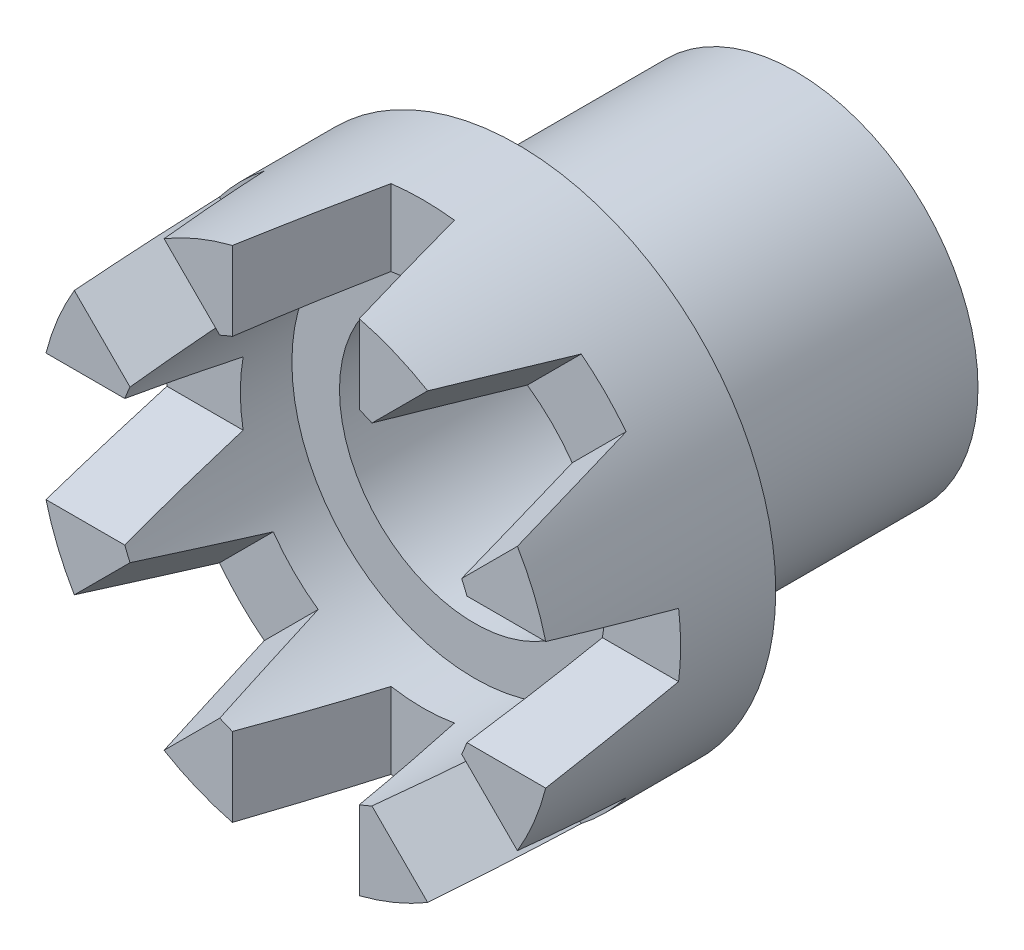
SolidWorks part; units mm, degrees
ref_plane "Спереди" through (0, 0, 0) normal (0, 0, 1) x (1, 0, 0)
ref_plane "Сверху" through (0, 0, 0) normal (0, 1, 0) x (1, 0, 0)
ref_plane "Справа" through (0, 0, 0) normal (1, 0, 0) x (0, 0, -1)
sketch "Эскиз1" plane through (0, 0, 0) normal (1, 0, 0) x (0, 0, -1)
  line L0 (0, 0) -> (130, 0) construction
  line L1 (0, 46) -> (0, 65)
  line L2 (0, 65) -> (56, 65)
  line L3 (56, 65) -> (56, 46)
  line L4 (56, 46) -> (126, 46)
  line L5 (126, 46) -> (126, 32)
  line L6 (126, 32) -> (123, 32)
  line L7 (123, 32) -> (123, 34)
  line L8 (123, 34) -> (45, 34)
  line L9 (45, 34) -> (45, 46)
  line L10 (45, 46) -> (0, 46)
  dimension "D1" = 19
  dimension "D2" = 56
  dimension "D3" = 70
  dimension "D4" = 14
  dimension "D5" = 3
  dimension "D6" = 2
  dimension "D7" = 78
  dimension "D8" = 46
  dimension "D9" = 34
revolve "Повернуть1" add sketch "Эскиз1" angle 360 about L0
sketch "Эскиз2" plane through (0, 0, 0) normal (1, 0, 0) x (0, 0, -1)
  line L0 (28, 0) -> (-22, 0) construction
  line L1 (0, 16) -> (0, -16)
  line L2 (0, 65) -> (0, -65) construction
  line L3 (0, -16) -> (32, -8)
  line L4 (32, -8) -> (32, 8)
  line L5 (0, 16) -> (32, 8)
  point P3 (32, 0)
  point P11 (0, 0)
extrude "Вытянуть1" cut sketch "Эскиз2" against normal blind 65 and the other way blind 65
sketch "Эскиз3" plane through (0, 0, 0) normal (0, 1, 0) x (1, 0, 0)
  line L0 (0, 28) -> (0, -22) construction
  line L1 (-16, 0) -> (16, 0)
  line L2 (16, 0) -> (8, 32)
  line L3 (8, 32) -> (-8, 32)
  line L4 (-16, 0) -> (-8, 32)
  point P3 (0, 32)
  point P9 (0, 0)
extrude "Вытянуть2" cut sketch "Эскиз3" against normal blind 65 and the other way blind 65
ref_plane "Плоскость4" through (0, 0, 0) normal (-0.7071, 0.7071, 0) x (-0.7071, -0.7071, 0)
sketch "Эскиз4" plane through (0, 0, 0) normal (-0.7071, 0.7071, 0) x (-0.7071, -0.7071, 0)
  line L0 (0, 28) -> (0, -22) construction
  line L1 (16, 0) -> (-16, 0)
  line L2 (-16, 0) -> (-8, -32)
  line L3 (-8, -32) -> (8, -32)
  line L4 (16, 0) -> (8, -32)
  point P3 (0, -32)
  point P9 (0, 0)
extrude "Вытянуть3" cut sketch "Эскиз4" against normal blind 65 and the other way blind 65
ref_plane "Плоскость5" through (0, 0, 0) normal (0.7071, 0.7071, 0) x (0, 0, -1)
sketch "Эскиз5" plane through (0, 0, 0) normal (0.7071, 0.7071, 0) x (0, 0, -1)
  line L0 (28, 0) -> (-22, 0) construction
  line L1 (0, 16) -> (0, -16)
  line L2 (0, -16) -> (32, -8)
  line L3 (32, -8) -> (32, 8)
  line L4 (0, 16) -> (32, 8)
  point P3 (32, 0)
  point P9 (0, 0)
extrude "Вытянуть4" cut sketch "Эскиз5" against normal blind 65 and the other way blind 65
